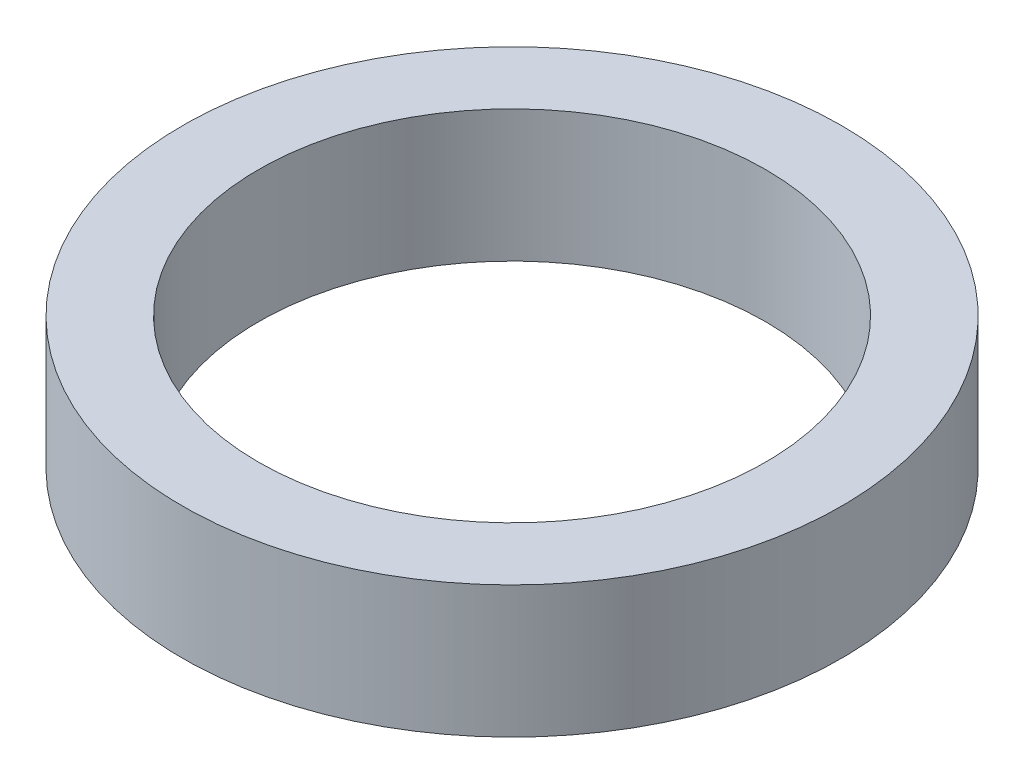
SolidWorks part; units mm, degrees
ref_plane "Front Plane" through (0, 0, 0) normal (0, 0, 1) x (1, 0, 0)
ref_plane "Top Plane" through (0, 0, 0) normal (0, 1, 0) x (1, 0, 0)
ref_plane "Right Plane" through (0, 0, 0) normal (1, 0, 0) x (0, 0, -1)
sketch "Sketch1" plane through (0, 0, 0) normal (0, 1, 0) x (1, 0, 0)
  circle A0 centre (0, 0) radius 65
  dimension "FLANGE_OD" = 130
extrude "Boss-Extrude1" add sketch "Sketch1" along normal blind 26
sketch "Sketch2" plane through (0, 0, 0) normal (0, 1, 0) x (1, 0, 0)
  circle A0 centre (0, 0) radius 50
  dimension "BORE_D" = 100
extrude "Cut-Extrude1" cut sketch "Sketch2" along normal through all
sketch "Sketch3" plane through (0, 26, 0) normal (0, 1, 0) x (1, 0, 0)
  circle A0 centre (0, 0) radius 30.0404 construction
  circle A1 centre (-30.0404, 0) radius 1.5372
  dimension "BOLT_D" = 3.0744
  dimension "BOLT_PCD" = 60.0808
extrude "Cut-Extrude2" cut sketch "Sketch3" against normal blind 18.2948 rebuild error yes
pattern_circular "CirPattern1" count 6 over 360 rebuild error yes
